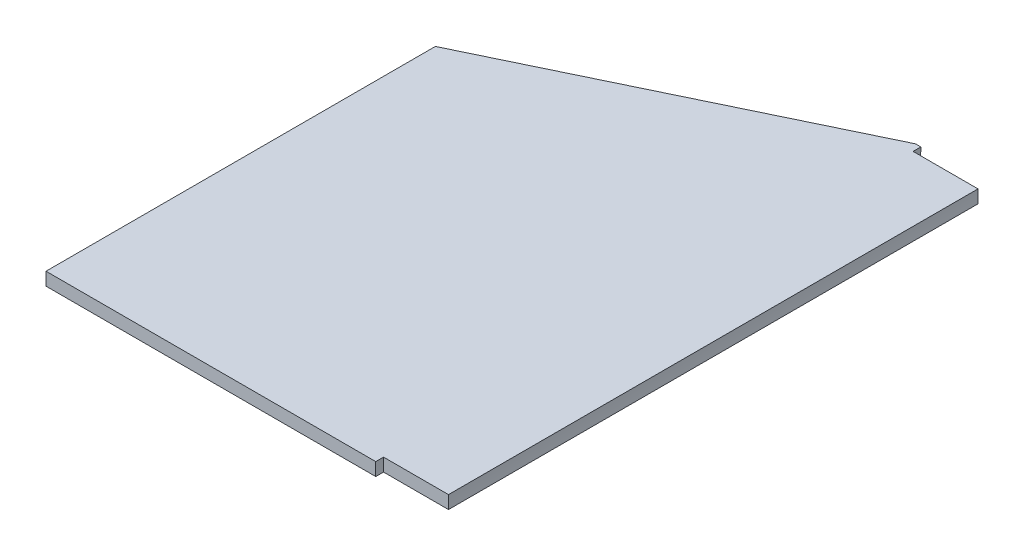
SolidWorks part; units mm, degrees
material "Thornel Mat VMA"
ref_plane "Front Plane" through (0, 0, 0) normal (0, 0, 1) x (1, 0, 0)
ref_plane "Top Plane" through (0, 0, 0) normal (0, 1, 0) x (1, 0, 0)
ref_plane "Right Plane" through (0, 0, 0) normal (1, 0, 0) x (0, 0, -1)
sketch "Sketch1" plane through (0, 0, 0) normal (0, 1, 0) x (1, 0, 0)
  line L0 (-125, 150) -> (-125, 0)
  line L1 (-125, 0) -> (0, 0)
  line L2 (0, 0) -> (0, 210) construction
  line L3 (0, 210) -> (-125, 150)
  line L15 (0, 0) -> (78.2, 0)
  line L17 (0, 210) -> (78.2, 210)
  line L18 (78.2, 0) -> (78.2, 210)
  dimension "D1" = 210
  dimension "D2" = 150
  dimension "D3" = 125
  dimension "D4" = 78.2
extrude "Boss-Extrude1" add sketch "Sketch1" along normal blind 2.5 and the other way blind 2.5
sketch "Sketch2" plane through (0, 0, -210) normal (0, 0, -1) x (-1, 0, 0)
  line L0 (-78.2, -2.5) -> (-78.2, 2.5) construction
  circle A0 centre (-78.2, 0) radius 51.2
  dimension "D1" = 102.4
extrude "Cut-Extrude1" cut sketch "Sketch2" against normal through all
sketch "Sketch3" plane through (0, 0, -210) normal (0, 0, -1) x (-1, 0, 0)
  line L0 (0, 0) -> (-78.2, 0) construction
  circle A0 centre (-78.2, 0) radius 76.2
  dimension "D2" = 152.4
  dimension "D1" = 78.2
extrude "Cut-Extrude2" cut sketch "Sketch3" against normal blind 3
sketch "Sketch4" plane through (0, 0, 0) normal (0, 0, 1) x (1, 0, 0)
  line L0 (0, 0) -> (78.2, 0) construction
  circle A0 centre (78.2, 0) radius 76.2
  dimension "D2" = 152.4
  dimension "D1" = 78.2
extrude "Cut-Extrude3" cut sketch "Sketch4" against normal blind 3
